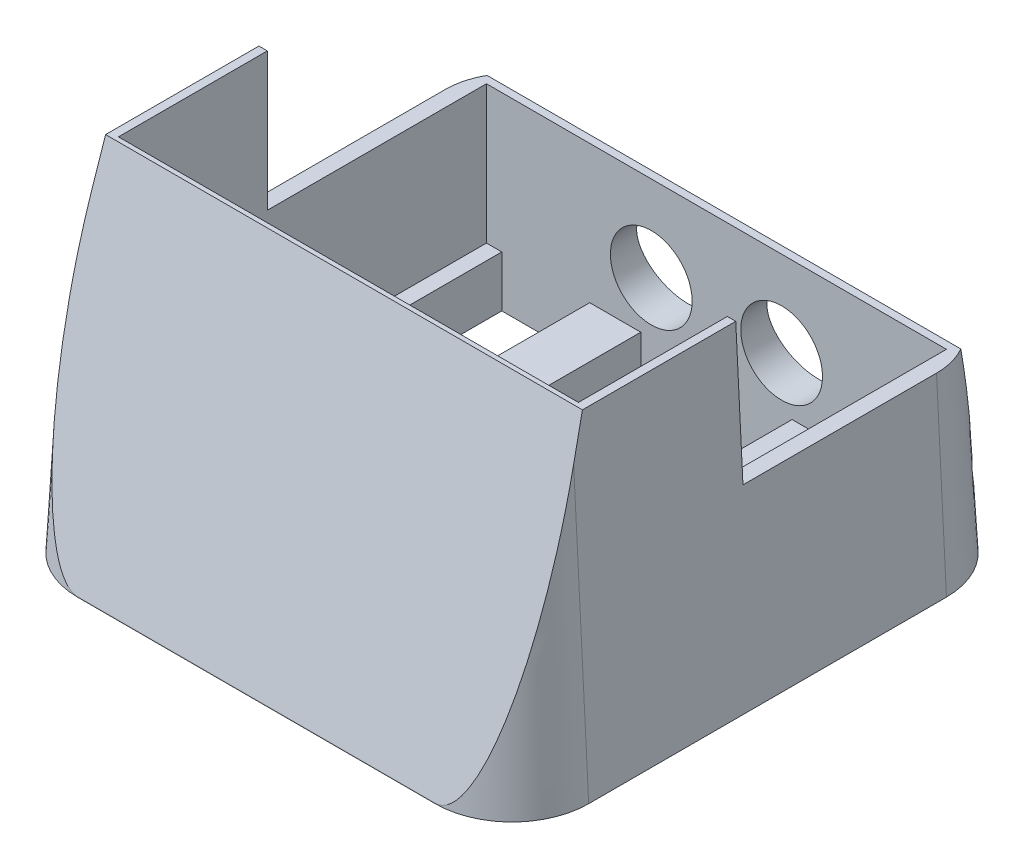
SolidWorks part; units mm, degrees
ref_plane "Front Plane" through (0, 0, 0) normal (0, 0, 1) x (1, 0, 0)
ref_plane "Top Plane" through (0, 0, 0) normal (0, 1, 0) x (1, 0, 0)
ref_plane "Right Plane" through (0, 0, 0) normal (1, 0, 0) x (0, 0, -1)
sketch "Sketch1" plane through (0, 0, 0) normal (0, 1, 0) x (1, 0, 0)
  line L0 (-35, 50) -> (35, 50)
  line L5 (50, 35) -> (50, -35)
  line L6 (-50, 35) -> (-50, -35)
  line L7 (-35, -50) -> (35, -50)
  arc A0 (35, -50) -> (50, -35) centre (35, -35) ccw
  arc A1 (-50, -35) -> (-35, -50) centre (-35, -35) ccw
  arc A2 (-50, 35) -> (-35, 50) centre (-35, 35) cw
  arc A3 (35, 50) -> (50, 35) centre (35, 35) cw
  point P14 (0, -50)
  point P19 (-50, 0)
  dimension "D3" = 15
  dimension "D4" = 15
  dimension "D5" = 15
  dimension "D6" = 15
  dimension "D1" = 100
  dimension "D2" = 100
extrude "Boss-Extrude1" add sketch "Sketch1" along normal blind 10
sketch "Sketch2" plane through (0, 10, 0) normal (0, 1, 0) x (1, 0, 0)
  line L0 (-50, 35) -> (-50, -35) construction
  line L1 (-42, 40) -> (-24.8, 40)
  line L2 (-42, 40) -> (-42, -3)
  line L3 (-42, -3) -> (-24.8, -3)
  line L4 (-24.8, 40) -> (-24.8, -3)
  line L5 (-42, 40) -> (-24.8, -3) construction
  line L6 (-42, -3) -> (-24.8, 40) construction
  line L7 (24.8, 40) -> (42, 40)
  line L8 (24.8, 40) -> (24.8, -3)
  line L9 (24.8, -3) -> (42, -3)
  line L10 (42, 40) -> (42, -3)
  line L11 (24.8, 40) -> (42, -3) construction
  line L12 (24.8, -3) -> (42, 40) construction
  line L13 (50, -35) -> (50, 35) construction
  line L15 (35, 50) -> (-35, 50) construction
  point P0 (-33.4, 18.5)
  point P5 (33.4, 18.5)
  dimension "D1" = 8
  dimension "D2" = 8
  dimension "D3" = 17.2
  dimension "D4" = 17.2
  dimension "D5" = 43
  dimension "D6" = 43
  dimension "D7" = 10
  dimension "D8" = 10
extrude "Cut-Extrude1" cut sketch "Sketch2" against normal through all
sketch "Sketch3" plane through (0, 10, 0) normal (0, 1, 0) x (1, 0, 0)
  line L1 (-40, -8) -> (40, -8)
  line L2 (-40, -8) -> (-40, -32)
  line L3 (-40, -32) -> (40, -32)
  line L4 (40, -8) -> (40, -32)
  line L5 (-40, -8) -> (40, -32) construction
  line L6 (-40, -32) -> (40, -8) construction
  line L7 (-45, -3) -> (45, -3)
  line L8 (-45, -3) -> (-45, -37)
  line L9 (-45, -37) -> (45, -37)
  line L10 (45, -3) -> (45, -37)
  line L11 (-45, -3) -> (45, -37) construction
  line L12 (-45, -37) -> (45, -3) construction
  line L13 (-35, -50) -> (35, -50) construction
  line L14 (-42, -3) -> (-24.8, -3) construction
  point P0 (0, -20)
  point P5 (0, -20)
  point P18 (0, -50)
  dimension "D1" = 24
  dimension "D2" = 80
  dimension "D3" = 34
  dimension "D4" = 90
extrude "Boss-Extrude3" add sketch "Sketch3" along normal blind 15
sketch "Sketch4" plane through (0, 10, 0) normal (0, 1, 0) x (1, 0, 0)
  line L0 (24.8, 40) -> (24.8, -3) construction
  line L3 (-24.8, 12.5) -> (24.8, 12.5)
  line L5 (-24.8, 24.5) -> (24.8, 24.5)
  line L6 (-24.8, 29.5) -> (24.8, 29.5)
  line L11 (-24.8, 7.5) -> (24.8, 7.5)
  line L12 (-24.8, 29.5) -> (-24.8, 24.5)
  line L13 (-24.8, -3) -> (-24.8, 40) construction
  line L14 (-24.8, 12.5) -> (-24.8, 7.5)
  line L15 (24.8, 12.5) -> (24.8, 7.5)
  line L16 (24.8, 29.5) -> (24.8, 24.5)
  point P4 (-24.8, 18.5)
  dimension "D1" = 5
  dimension "D2" = 12
  dimension "D3" = 5
  dimension "D4" = 6
extrude "Boss-Extrude4" add sketch "Sketch4" along normal blind 10
sketch "Sketch5" plane through (0, 20, 0) normal (0, 1, 0) x (1, 0, 0)
  line L0 (-24.8, 7.5) -> (24.8, 7.5) construction
  line L1 (-24.8, 29.5) -> (-9.8, 29.5)
  line L2 (-24.8, 29.5) -> (-24.8, 7.5)
  line L3 (-24.8, 7.5) -> (-9.8, 7.5)
  line L4 (-9.8, 29.5) -> (-9.8, 7.5)
  line L6 (24.8, 29.5) -> (9.8, 29.5)
  line L7 (24.8, 29.5) -> (24.8, 7.5)
  line L8 (24.8, 7.5) -> (9.8, 7.5)
  line L9 (9.8, 29.5) -> (9.8, 7.5)
  dimension "D1" = 15
  dimension "D2" = 15
extrude "Boss-Extrude5" add sketch "Sketch5" along normal blind 5
sketch "Sketch6" plane through (0, 10, 0) normal (0, 1, 0) x (1, 0, 0)
  line L1 (-45, -37) -> (45, -37)
  line L2 (-45, -37) -> (-45, 40)
  line L3 (-45, 40) -> (45, 40)
  line L4 (45, -37) -> (45, 40)
  line L5 (45, -37) -> (45, -3) construction
  line L6 (-24.8, 40) -> (-42, 40) construction
  line L7 (-50, 35) -> (-50, -35) construction
  line L8 (-35, -50) -> (35, -50) construction
  line L9 (50, -35) -> (50, 35) construction
  line L10 (35, 50) -> (-35, 50) construction
  line L11 (-50, 35) -> (-50, -35)
  line L12 (-35, -50) -> (35, -50)
  line L13 (50, -35) -> (50, 35)
  line L14 (35, 50) -> (-35, 50)
  arc A0 (-50, -35) -> (-35, -50) centre (-35, -35) ccw construction
  arc A1 (35, -50) -> (50, -35) centre (35, -35) ccw construction
  arc A2 (50, 35) -> (35, 50) centre (35, 35) ccw construction
  arc A3 (-35, 50) -> (-50, 35) centre (-35, 35) ccw construction
  arc A4 (-50, -35) -> (-35, -50) centre (-35, -35) ccw
  arc A5 (35, -50) -> (50, -35) centre (35, -35) ccw
  arc A6 (50, 35) -> (35, 50) centre (35, 35) ccw
  arc A7 (-35, 50) -> (-50, 35) centre (-35, 35) ccw
extrude "Boss-Extrude6" add sketch "Sketch6" along normal up to surface (15 mm away) up to face at (0, 25, 20)
sketch "Sketch9" plane through (0, 25, 0) normal (0, 1, 0) x (1, 0, 0)
  line L22 (-50, 35) -> (-50, -35) construction
  line L23 (-35, -50) -> (35, -50) construction
  line L24 (50, -35) -> (50, 35) construction
  line L25 (35, 50) -> (-35, 50) construction
  line L26 (-45, 35) -> (-45, -35)
  line L27 (-35, -45) -> (35, -45)
  line L28 (45, -35) -> (45, 35)
  line L29 (35, 45) -> (-35, 45)
  line L30 (-45, 35) -> (-45, -32)
  line L32 (45, -32) -> (45, 35)
  line L34 (-50, 35) -> (-50, -35)
  line L35 (-35, -50) -> (35, -50)
  line L36 (50, -35) -> (50, 35)
  line L37 (35, 50) -> (-35, 50)
  line L38 (45, -32) -> (-45, -32)
  line L39 (-40, -32) -> (40, -32) construction
  line L40 (43.6603, 40) -> (-43.6603, 40)
  line L41 (45, 40) -> (-45, 40) construction
  arc A23 (-50, -35) -> (-35, -50) centre (-35, -35) ccw construction
  arc A24 (35, -50) -> (50, -35) centre (35, -35) ccw construction
  arc A25 (50, 35) -> (35, 50) centre (35, 35) ccw construction
  arc A26 (-35, 50) -> (-50, 35) centre (-35, 35) ccw construction
  arc A27 (-45, -35) -> (-35, -45) centre (-35, -35) ccw
  arc A28 (35, -45) -> (45, -35) centre (35, -35) ccw
  arc A29 (45, 35) -> (35, 45) centre (35, 35) ccw
  arc A30 (-35, 45) -> (-45, 35) centre (-35, 35) ccw
  arc A33 (45, 35) -> (43.6603, 40) centre (35, 35) ccw
  arc A34 (-43.6603, 40) -> (-45, 35) centre (-35, 35) ccw
  arc A35 (-50, -35) -> (-35, -50) centre (-35, -35) ccw
  arc A36 (35, -50) -> (50, -35) centre (35, -35) ccw
  arc A37 (50, 35) -> (35, 50) centre (35, 35) ccw
  arc A38 (-35, 50) -> (-50, 35) centre (-35, 35) ccw
  dimension "D1" = 5
extrude "Boss-Extrude8" add sketch "Sketch9" along normal blind 39
chamfer "Chamfer1" distance 64 angle 3 8 edges at (0, 64, 50) (45.6066, 64, 45.6066) (-45.6066, 64, 45.6066) (50, 64, 0) (-50, 64, 0) (45.6066, 64, -45.6066) (-45.6066, 64, -45.6066) (0, 64, -50) first distance on face at (0, 32, 50) first distance on face at (44.0533, 32, 44.0533) first distance on face at (-44.0533, 32, 44.0533) first distance on face at (50, 32, 0) first distance on face at (-50, 32, 0) first distance on face at (44.0533, 32, -44.0533) first distance on face at (-44.0533, 32, -44.0533) first distance on face at (0, 32, -50)
chamfer "Chamfer2" distance 64 angle 10 1 edges at (0, 64, -46.6459) tangent propagation no first distance on face at (0, 32, -48.323)
chamfer "Chamfer3" distance 64 angle 12 1 edges at (0, 64, 46.6459) tangent propagation no first distance on face at (0, 32, 48.323)
sketch "Sketch10" plane through (0, 1.3075, 0) normal (-1, 0, 0) x (0, 0, 1)
  line L0 (-35, 62.6925) -> (32.8702, 62.6925) construction
  line L1 (2.8702, 62.6925) -> (-47.1298, 62.6925)
  line L2 (2.8702, 62.6925) -> (2.8702, 35.6925)
  line L3 (2.8702, 35.6925) -> (-47.1298, 35.6925)
  line L4 (-47.1298, 62.6925) -> (-47.1298, 35.6925)
  dimension "D1" = 50
  dimension "D2" = 27
  dimension "D3" = 30
extrude "Cut-Extrude3" cut sketch "Sketch10" against normal through all and the other way through all
sketch "Sketch15" plane through (0, 0, -40) normal (0, 0, 1) x (1, 0, 0)
  line L1 (12.75, 20.25) -> (-12.75, 20.25) construction
  line L2 (0, -35.2) -> (0, 35.2) construction
  line L3 (24.8, 10) -> (-24.8, 10) construction
  circle A0 centre (-12.75, 20.25) radius 8
  circle A1 centre (12.75, 20.25) radius 8
  point P9 (0, 20.25)
  dimension "D3" = 16
  dimension "D4" = 16
  dimension "D1" = 10.25
  dimension "D5" = 25.5
extrude "Cut-Extrude5" cut sketch "Sketch15" against normal through all
sketch "Sketch17" plane through (0, 0, -29.5) normal (0, 0, -1) x (-1, 0, 0)
  line L8 (-9.8, 25) -> (-24.8, 25)
  line L9 (-24.8, 10) -> (24.8, 10)
  line L10 (-24.8, 10) -> (24.8, 10)
  line L11 (24.8, 10) -> (24.8, 25)
  line L12 (24.8, 25) -> (9.8, 25)
  line L13 (9.8, 25) -> (9.8, 20)
  line L14 (9.8, 20) -> (-9.8, 20)
  line L15 (-9.8, 20) -> (-9.8, 25)
  line L16 (-9.8, 25) -> (-24.8, 25)
  line L20 (24.8, 25) -> (9.8, 25)
  line L21 (9.8, 25) -> (9.8, 20)
  line L22 (9.8, 20) -> (-9.8, 20)
  line L23 (-9.8, 20) -> (-9.8, 25)
  line L24 (24.8, 10) -> (24.8, 25)
  line L25 (-24.8, 25) -> (-24.8, 10)
  line L26 (-24.8, 25) -> (-24.8, 10)
  dimension "D1" = 0
extrude "Cut-Extrude6" cut sketch "Sketch17" against normal blind 2.5
sketch "Sketch18" plane through (0, 0, 0) normal (0, -1, 0) x (1, 0, 0)
  line L0 (-24.8, -40) -> (-42, -40) construction
  line L1 (-14.8, -40) -> (14.8, -40)
  line L2 (-14.8, -40) -> (-14.8, 3)
  line L3 (-14.8, 3) -> (14.8, 3)
  line L4 (14.8, -40) -> (14.8, 3)
  line L5 (-24.8, 3) -> (-24.8, -40) construction
  line L6 (24.8, -40) -> (24.8, 3) construction
  line L7 (24.8, 3) -> (42, 3) construction
  dimension "D1" = 10
  dimension "D2" = 10
extrude "Cut-Extrude7" cut sketch "Sketch18" against normal up to surface (10 mm away) up to face at (0, 10, -18.5)
sketch "Sketch20" plane through (0, 25, 0) normal (0, -1, 0) x (1, 0, 0)
  line L0 (-45, -35) -> (-45, -40) construction
  line L1 (-45, -40) -> (-43.6603, -40) construction
  line L2 (45, -40) -> (45, -35) construction
  line L3 (43.6603, -40) -> (45, -40) construction
  line L4 (-45, -35) -> (-45, -40)
  line L5 (-45, -40) -> (-43.6603, -40)
  line L6 (45, -40) -> (45, -35)
  line L7 (43.6603, -40) -> (45, -40)
  arc A0 (-45, -35) -> (-43.6603, -40) centre (-35, -35) ccw construction
  arc A1 (43.6603, -40) -> (45, -35) centre (35, -35) ccw construction
  arc A2 (-45, -35) -> (-43.6603, -40) centre (-35, -35) ccw
  arc A3 (43.6603, -40) -> (45, -35) centre (35, -35) ccw
extrude "Cut-Extrude8" cut sketch "Sketch20" against normal blind 15
sketch "Sketch21" plane through (0, 0, 0) normal (0, -1, 0) x (1, 0, 0)
  line L0 (-14.8, 3) -> (-14.8, -40) construction
  line L1 (-14.8, 3) -> (14.8, 3)
  line L2 (-14.8, 3) -> (-14.8, -30)
  line L3 (-14.8, -30) -> (14.8, -30)
  line L4 (14.8, 3) -> (14.8, -30)
  line L5 (14.8, -40) -> (14.8, 3) construction
  line L7 (-14.8, -40) -> (14.8, -40) construction
  line L8 (14.8, 3) -> (-14.8, 3) construction
  dimension "D2" = 10
extrude "Boss-Extrude10" add sketch "Sketch21" against normal blind 2.5
sketch "Sketch23" plane through (0, 10, 0) normal (0, 1, 0) x (1, 0, 0)
  line L0 (-24.8, 27) -> (-9.8, 27) construction
  line L2 (-22.75, 27) -> (-22.75, 40)
  line L4 (22.75, 27) -> (22.75, 40)
  line L5 (24.8, 40) -> (14.8, 40) construction
  line L6 (-24.8, 27) -> (-24.8, 40) construction
  line L7 (24.8, 40) -> (24.8, 27) construction
  line L8 (24.8, 40) -> (24.8, 27)
  line L9 (-24.8, 27) -> (-24.8, 40)
  line L10 (-22.75, 27) -> (-24.8, 27)
  line L11 (22.75, 27) -> (24.8, 27)
  line L12 (24.8, 40) -> (22.75, 40)
  line L13 (-22.75, 40) -> (-24.8, 40)
  dimension "D1" = 45.5
  dimension "D2" = 2.05
extrude "Boss-Extrude11" add sketch "Sketch23" along normal up to surface (15 mm away) up to face at (-17.3, 25, -17.25)
sketch "Sketch24" plane through (0, 64, 0) normal (0, 1, 0) x (1, 0, 0)
  line L1 (-45, -32) -> (45, -32)
  line L2 (-45, -32) -> (-45, 40)
  line L3 (-45, 40) -> (45, 40)
  line L4 (45, -32) -> (45, 40)
extrude "Cut-Extrude9" cut sketch "Sketch24" against normal up to surface (54 mm away) up to face at (-19.8, 10, -2.25)
